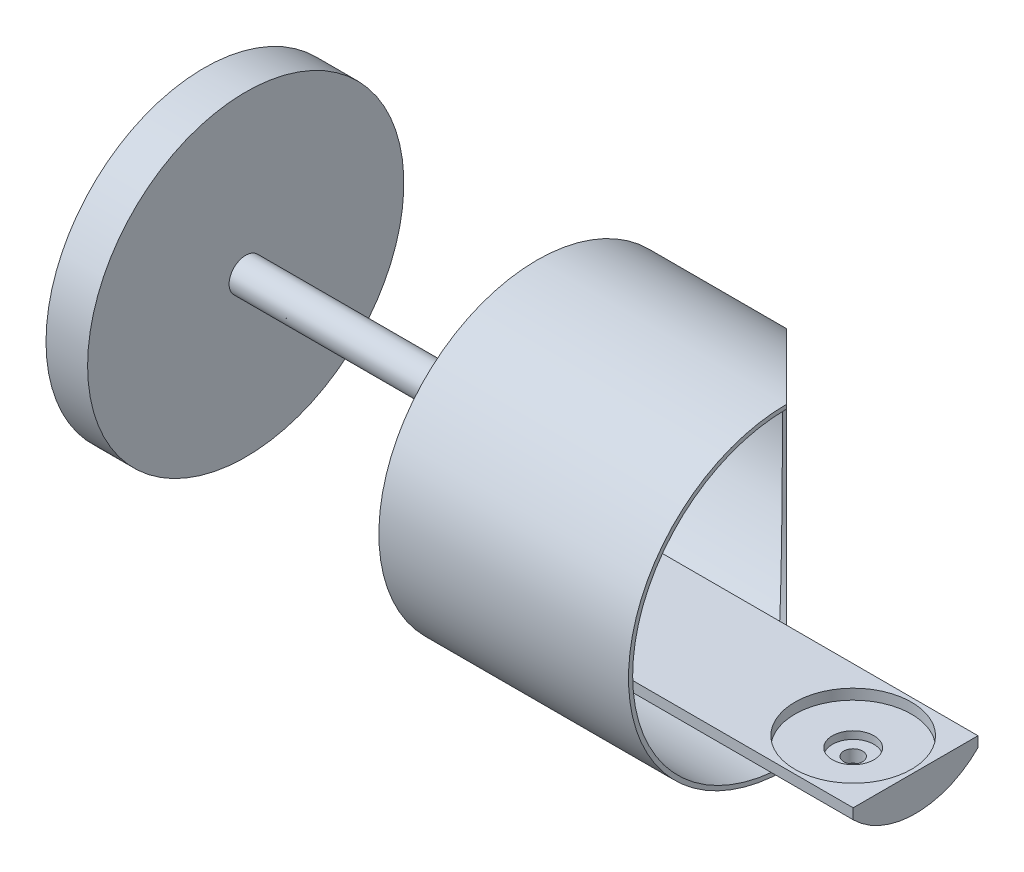
SolidWorks part; units mm, degrees
ref_plane "Front Plane" through (0, 0, 0) normal (0, 0, 1) x (1, 0, 0)
ref_plane "Top Plane" through (0, 0, 0) normal (0, 1, 0) x (1, 0, 0)
ref_plane "Right Plane" through (0, 0, 0) normal (1, 0, 0) x (0, 0, -1)
sketch "Sketch12" plane through (0, 0, 0) normal (-1, 0, 0) x (0, 0, 1)
  circle A0 centre (0, 19.5) radius 4
extrude "Boss-Extrude5" add sketch "Sketch12" along normal blind 70
sketch "Sketch13" plane through (-70, 0, 0) normal (-1, 0, 0) x (0, 0, 1)
  circle A0 centre (0, 19.5) radius 38
extrude "Boss-Extrude6" add sketch "Sketch13" along normal blind 10
sketch "Sketch14" plane through (-80, 0, 0) normal (-1, 0, 0) x (0, 0, 1)
  circle A0 centre (0, 19.5) radius 29
extrude "Cut-Extrude1" cut sketch "Sketch14" against normal blind 5
sketch "Sketch15" plane through (0, 0, 0) normal (1, 0, 0) x (0, 0, -1)
  circle A0 centre (0, 19.5) radius 38
extrude "Boss-Extrude7" add sketch "Sketch15" along normal blind 60
sketch "Sketch17" plane through (0, 0, 0) normal (0, 0, 1) x (1, 0, 0)
  line L5 (60, 57.5) -> (60, -18.5)
  arc A1 (60, 57.5) -> (60, -18.5) centre (60, 19.5) ccw
  point P5 (60, 19.0101)
extrude "Cut-Extrude2" cut sketch "Sketch17" against normal blind 80
shell "Shell2" thickness 1 removed face at (22, 19.5, -19) removed face at (41, 19.5, 0) removed face at (60, 19.5, 19)
sketch "Sketch18" plane through (1, 0, 0) normal (1, 0, 0) x (0, 0, -1)
  circle A0 centre (0, 19.5) radius 15
extrude "Boss-Extrude8" add sketch "Sketch18" along normal blind 20
sketch "Sketch19" plane through (1, 0, 0) normal (1, 0, 0) x (0, 0, -1)
  line L1 (15, -3.5) -> (-15, -3.5)
  line L9 (-15, -3.5) -> (-15, -6)
  line L10 (15, -3.5) -> (15, -6)
  arc A0 (-15, -6) -> (15, -6) centre (0, 9) ccw
extrude "Boss-Extrude13" add sketch "Sketch19" along normal blind 90 contours A0 L10 L1 L9
sketch "Sketch20" plane through (0, -3.5, 0) normal (0, 1, 0) x (1, 0, 0)
  circle A0 centre (76, 0) radius 14
extrude "Cut-Extrude3" cut sketch "Sketch20" against normal blind 2.5
sketch "Sketch21" plane through (0, -6, 0) normal (0, 1, 0) x (1, 0, 0)
  circle A0 centre (76, 0) radius 5
extrude "Cut-Extrude4" cut sketch "Sketch21" against normal blind 1.8
sketch "Sketch22" plane through (0, -7.8, 0) normal (0, 1, 0) x (1, 0, 0)
  circle A0 centre (76, 0) radius 2.25
extrude "Cut-Extrude5" cut sketch "Sketch22" against normal blind 3
